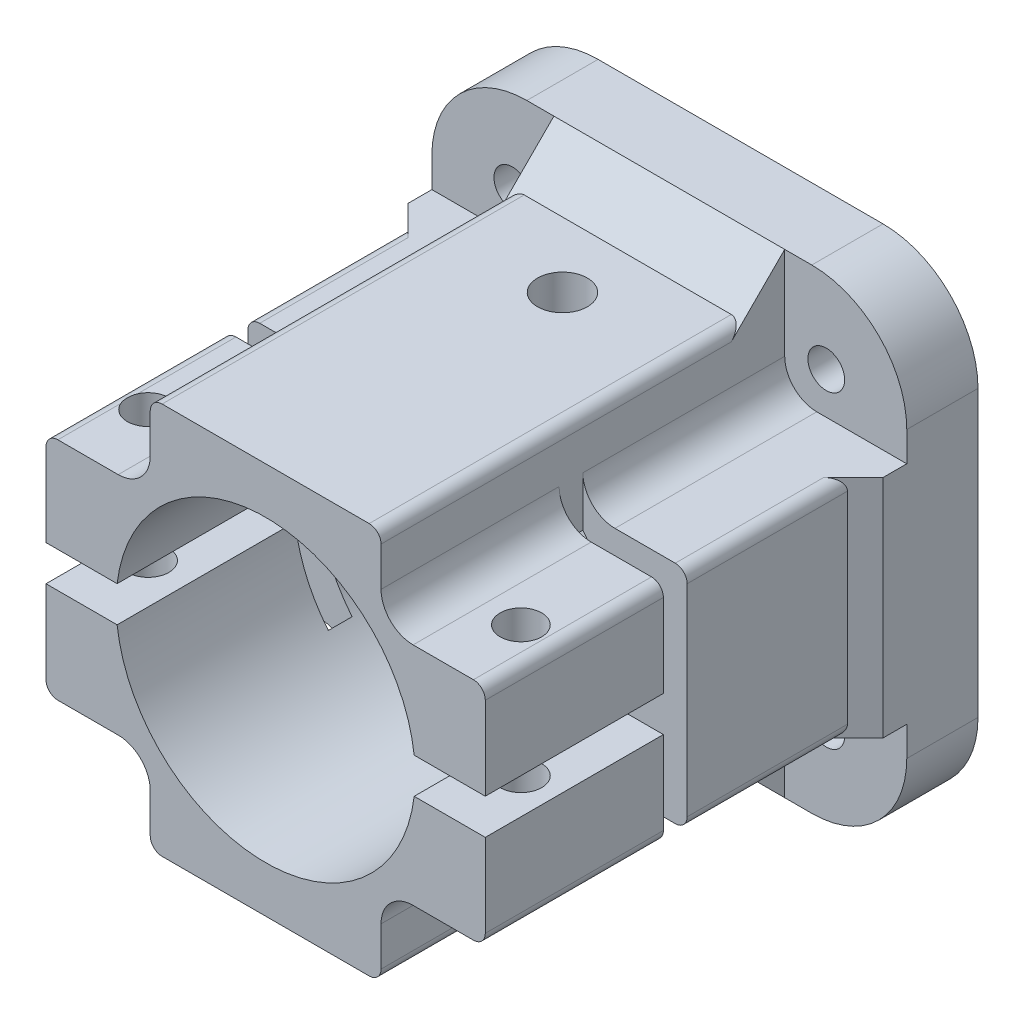
SolidWorks part; units mm, degrees
material "6061 合金"
ref_plane "前视基准面" through (0, 0, 0) normal (0, 0, 1) x (1, 0, 0)
ref_plane "上视基准面" through (0, 0, 0) normal (0, 1, 0) x (1, 0, 0)
ref_plane "右视基准面" through (0, 0, 0) normal (1, 0, 0) x (0, 0, -1)
sketch "草图1" plane through (0, 0, 0) normal (0, 0, 1) x (1, 0, 0)
  line L0 (-15.72, 23.2982) -> (-15.72, -24.751) construction
  line L1 (-20, -20) -> (20, -20)
  line L2 (-20, -20) -> (-20, 20)
  line L3 (-20, 20) -> (20, 20)
  line L4 (20, -20) -> (20, 20)
  line L5 (-20, -20) -> (20, 20) construction
  line L6 (-20, 20) -> (20, -20) construction
  line L7 (0, 20) -> (0, 0) construction
  line L8 (0, 0) -> (15.0364, 0) construction
  circle A0 centre (-13.22, 13) radius 1.55
  circle A1 centre (0, 0) radius 12.5
  circle A2 centre (13.22, 13) radius 1.55
  circle A3 centre (13.22, -13) radius 1.55
  circle A4 centre (-13.22, -13) radius 1.55
  point P0 (0, 0)
  dimension "D6" = 3.1
  dimension "D5" = 6.78
  dimension "D7" = 25
  dimension "D1" = 40
  dimension "D2" = 40
  dimension "D3" = 4.28
  dimension "D4" = 7
extrude "凸台-拉伸1" add sketch "草图1" along normal blind 6
sketch "草图2" plane through (0, 0, 6) normal (0, 0, 1) x (1, 0, 0)
  line L0 (-9.72, 9.5) -> (-9.72, 16.5)
  line L1 (-9.72, -16.5) -> (9.72, -16.5)
  line L2 (-18.5, -9.5) -> (-18.5, 9.5)
  line L3 (0, 0) -> (0, 20) construction
  line L4 (18.5, -9.5) -> (18.5, 9.5)
  line L5 (-10.6376, -10.6376) -> (16.5, 16.5) construction
  line L6 (-16.5, 16.5) -> (10.6376, -10.6376) construction
  line L7 (-9.72, 9.5) -> (-18.5, 9.5)
  line L8 (-9.72, 16.5) -> (9.72, 16.5)
  line L9 (20, 20) -> (-20, 20) construction
  line L10 (0, 0) -> (18.5, 0) construction
  line L11 (9.72, 9.5) -> (18.5, 9.5)
  line L12 (9.72, 9.5) -> (9.72, 16.5)
  line L13 (9.72, -9.5) -> (18.5, -9.5)
  line L14 (9.72, -9.5) -> (9.72, -16.5)
  line L15 (-9.72, -9.5) -> (-9.72, -16.5)
  line L16 (-9.72, -9.5) -> (-18.5, -9.5)
  circle A4 centre (0, 0) radius 12.5 construction
  circle A5 centre (0, 0) radius 12.5
  point P0 (0, 0)
  dimension "D1" = 18.5
  dimension "D4" = 16.5
extrude "凸台-拉伸2" add sketch "草图2" along normal blind 34
sketch "草图4" plane through (0, 9.5, 0) normal (0, 1, 0) x (1, 0, 0)
  line L0 (15.5, -43.489) -> (15.5, -9.113) construction
  line L1 (-15.9, -43.489) -> (-15.9, -8.3491) construction
  line L2 (18.5, -40) -> (18.5, -6) construction
  line L3 (-18.5, -40) -> (-18.5, -6) construction
  line L4 (-9.72, -40) -> (-18.5, -40) construction
  line L5 (18.5, -40) -> (9.72, -40) construction
  circle A0 centre (-15.9, -34) radius 1.75
  circle A1 centre (15.5, -34) radius 1.75
  dimension "D3" = 3.5
  dimension "D4" = 3.5
  dimension "D5" = 6
  dimension "D6" = 6
  dimension "D1" = 3
  dimension "D2" = 2.6
extrude "切除-拉伸1" cut sketch "草图4" against normal through all
chamfer "倒角1" distance 3.5 angle 45 2 edges at (0, -16.5, 6) (0, 16.5, 6)
chamfer "倒角2" distance 3.5 angle 45 2 edges at (-18.5, 0, 6) (18.5, 0, 6)
fillet "圆角3" radius 2.7 4 edges at (-9.72, 9.5, 23) (-9.72, -9.5, 23) (9.72, -9.5, 23) (9.72, 9.5, 23)
fillet "圆角4" radius 8 4 edges at (-20, -20, 3) (20, -20, 3) (20, 20, 3) (-20, 20, 3)
sketch "草图5" plane through (0, 0, 0) normal (0, 0, -1) x (-1, 0, 0)
  circle A0 centre (0, 0) radius 12.5
extrude "凸台-拉伸3" add sketch "草图5" against normal blind 3
sketch "草图6" plane through (0, 0, 3) normal (0, 0, 1) x (1, 0, 0)
  circle A0 centre (0, 4) radius 1.55
  circle A1 centre (0, -4) radius 1.55
  dimension "D1" = 3.1
  dimension "D2" = 4
  dimension "D3" = 3.1
  dimension "D4" = 4
extrude "切除-拉伸2" cut sketch "草图6" against normal through all
sketch "草图8" plane through (0, 0, 0) normal (0, 0, -1) x (-1, 0, 0)
  circle A0 centre (-13.22, 13) radius 1.55
  circle A1 centre (-13.22, 13) radius 3
  circle A2 centre (13.22, 13) radius 1.55
  circle A3 centre (13.22, 13) radius 3
  circle A4 centre (-13.22, -13) radius 3
  circle A5 centre (13.22, -13) radius 3
  circle A6 centre (-13.22, -13) radius 1.55
  circle A7 centre (13.22, -13) radius 1.55
  dimension "D1" = 6
  dimension "D2" = 6
  dimension "D3" = 6
  dimension "D4" = 6
extrude "凸台-拉伸4" add sketch "草图8" along normal blind 1.5
sketch "草图9" plane through (0, 0, 40) normal (0, 0, 1) x (1, 0, 0)
  line L0 (-25.7131, 0) -> (26.7479, 0) construction
  line L2 (-21.2464, 1.5) -> (23.5166, 1.5)
  line L3 (-21.2464, 1.5) -> (-21.2464, -1.5)
  line L4 (-21.2464, -1.5) -> (23.5166, -1.5)
  line L5 (23.5166, 1.5) -> (23.5166, -1.5)
  dimension "D1" = 1.5
  dimension "D2" = 1.5
extrude "切除-拉伸3" cut sketch "草图9" against normal blind 15
sketch "草图10" plane through (-18.5, 0, 0) normal (-1, 0, 0) x (0, 0, 1)
  line L0 (40, 16.5) -> (9.5, 16.5) construction
  line L1 (25, 14.5) -> (23, 14.5)
  line L2 (25, 14.5) -> (25, -14.5)
  line L3 (25, -14.5) -> (23, -14.5)
  line L4 (23, 14.5) -> (23, -14.5)
  line L5 (40, -16.5) -> (9.5, -16.5) construction
  line L6 (25, 1.5) -> (25, -1.5) construction
  dimension "D1" = 2
  dimension "D2" = 2
  dimension "D3" = 2
  dimension "D4" = 0
extrude "切除-拉伸4" cut sketch "草图10" against normal up to surface (8.78 mm away) up to face at (-9.72, 15.48, 20.3)
sketch "草图11" plane through (18.5, 0, 0) normal (1, 0, 0) x (0, 0, -1)
  line L0 (-40, -16.5) -> (-9.5, -16.5) construction
  line L1 (-25, 15.2469) -> (-23, 15.2469)
  line L2 (-25, 15.2469) -> (-25, -14.5)
  line L3 (-25, -14.5) -> (-23, -14.5)
  line L4 (-23, 15.2469) -> (-23, -14.5)
  dimension "D1" = 2
  dimension "D2" = 2
extrude "切除-拉伸5" cut sketch "草图11" against normal up to surface (8.78 mm away) up to face at (9.72, 15.48, 20.3)
fillet "圆角5" radius 1 12 edges at (-9.72, 16.5, 24.75) (9.72, 16.5, 24.75) (18.5, 9.5, 32.5) (18.5, 9.5, 16.25) (18.5, -9.5, 32.5) (18.5, -9.5, 16.25) (9.72, -16.5, 24.75) (-18.5, 9.5, 16.25) (-18.5, -9.5, 16.25) (-9.72, -16.5, 24.75) (-18.5, -9.5, 32.5) (-18.5, 9.5, 32.5)
sketch "草图12" plane through (0, 16.5, 0) normal (0, 1, 0) x (1, 0, 0)
  line L0 (12, 0) -> (-12, 0) construction
  circle A0 centre (0, -15) radius 2.1
  dimension "D2" = 4.2
  dimension "D1" = 15
extrude "切除-拉伸6" cut sketch "草图12" against normal through all
sketch "草图14" plane through (0, 0, 40) normal (0, 0, 1) x (1, 0, 0)
  circle A0 centre (0, 0) radius 12.6
  dimension "D1" = 25.2
extrude "切除-拉伸7" cut sketch "草图14" against normal up to surface (37 mm away) up to face at (1.55, -4, 3)
